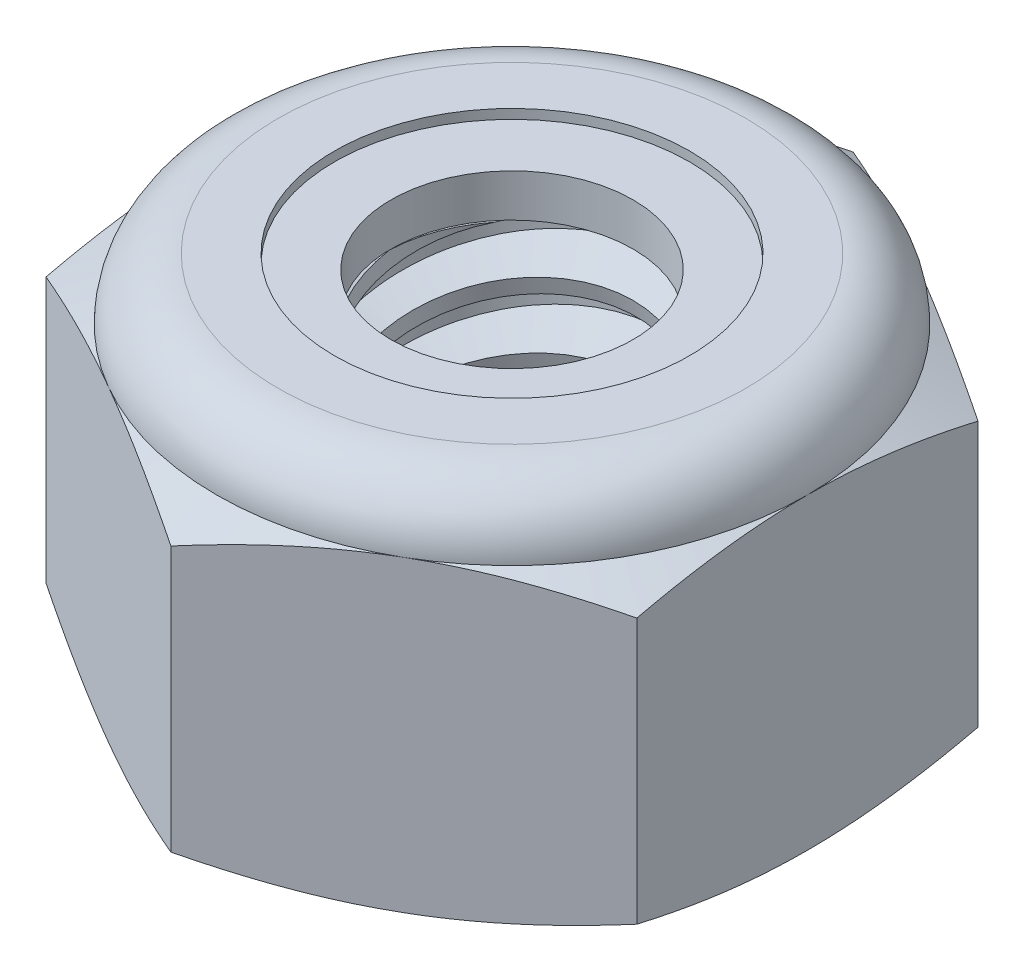
SolidWorks part; units mm, degrees
material "Alloy Steel"
ref_plane "Front" through (0, 0, 0) normal (0, 0, 1) x (1, 0, 0)
ref_plane "Top" through (0, 0, 0) normal (0, 1, 0) x (1, 0, 0)
ref_plane "Right" through (0, 0, 0) normal (1, 0, 0) x (0, 0, -1)
sketch "Sketch1" plane through (0, 0, 0) normal (0, 1, 0) x (1, 0, 0)
  line L1 (0, 5.4993) -> (-4.7625, 2.7496)
  line L2 (-4.7625, 2.7496) -> (-4.7625, -2.7496)
  line L3 (-4.7625, -2.7496) -> (0, -5.4993)
  line L4 (0, -5.4993) -> (4.7625, -2.7496)
  line L5 (4.7625, -2.7496) -> (4.7625, 2.7496)
  line L6 (4.7625, 2.7496) -> (0, 5.4993)
  circle A0 centre (0, 0) radius 4.7625 construction
  dimension "Hex Flats" = 9.525
extrude "Extrude1" add sketch "Sketch1" along normal blind 5.9531
sketch "Sketch2" plane through (0, 0, 0) normal (1, 0, 0) x (0, 0, -1)
  line L0 (-2.413, 0) -> (-2.413, 5.9531) construction
  line L1 (0, 0) -> (2.413, 0)
  line L2 (0, 0) -> (0, 5.9531)
  line L3 (0, 5.9531) -> (2.413, 5.9531)
  line L4 (2.413, 0) -> (2.413, 5.9531)
  line L5 (-2.7496, 5.9531) -> (2.7496, 5.9531) construction
  line L7 (0, -2.413) -> (0, 0) construction
  dimension "Thread Dia" = 4.826
revolve "Revolve1" add sketch "Sketch2" angle 360 about L7
sketch "Sketch3" plane through (0, 0, 0) normal (1, 0, 0) x (0, 0, -1)
  line L0 (2.413, 5.9531) -> (-2.413, 5.9531) construction
  line L1 (-2.413, 5.9531) -> (-2.413, 4.8948) construction
  line L2 (-2.413, 4.8948) -> (2.413, 5.9531) construction
  line L3 (2.413, 5.9531) -> (2.4413, 5.8239) construction
  line L4 (2.4413, 5.8239) -> (2.6397, 4.9194)
  line L5 (2.6397, 4.9194) -> (2.0093, 5.1197)
  line L6 (2.0093, 5.1197) -> (1.9526, 5.3781)
  line L7 (1.9526, 5.3781) -> (2.4413, 5.8239)
  line L8 (1.981, 5.2489) -> (2.5405, 5.3716) construction
  line L9 (2.413, 5.9531) -> (2.413, 5.3437) construction
  line L10 (2.413, 5.3437) -> (-2.413, 4.2853) construction
  line L11 (-2.413, 4.2853) -> (-2.413, 4.8948) construction
  line L12 (-0.2497, 5.9531) -> (0.2497, 3.6759) construction
  line L13 (-2.413, 0) -> (-2.413, 5.9531) construction
  line L14 (0, 5.9531) -> (2.413, 5.9531) construction
  line L15 (2.413, 0) -> (2.413, 5.9531) construction
  point P13 (0, 4.8145)
  dimension "D1" = 0.1323
  dimension "D2" = 0.2646
  dimension "Thread Pitch" = 1.0583
  dimension "D4" = 60
  dimension "D5" = 1.0583
revolve "Cut-Revolve1" cut sketch "Sketch3" angle 360 about L12
pattern_linear "LPattern1" count 6 spacing 1.0583 along (0, -1, 0) count 2 spacing 1.0583 along (0, 1, 0) of "Cut-Revolve1"
sketch "Sketch4" plane through (0, 0, 0) normal (1, 0, 0) x (0, 0, -1)
  line L0 (0, 5.9531) -> (2.413, 5.9531)
  line L1 (2.413, 5.9531) -> (1.9526, 5.7385)
  line L2 (1.9526, 5.7385) -> (1.9526, 0.2147)
  line L3 (1.9526, 0.2147) -> (2.413, 0)
  line L4 (2.413, 0) -> (0, 0)
  line L5 (0, 0) -> (0, 5.9531)
  line L6 (2.413, 0) -> (2.413, 5.9531) construction
  line L7 (0, 5.9531) -> (2.413, 5.9531) construction
  line L8 (0, 0) -> (2.413, 0) construction
  line L9 (0, 0) -> (0, 5.9531) construction
  line L10 (0, 5.9531) -> (0, 6.4611) construction
  dimension "D1" = 25
revolve "Cut-Revolve2" cut sketch "Sketch4" angle 360 about L10
combine bodies "Combine1" operation type subtract main body 112 bodies to subtract 111
sketch "Sketch5" plane through (0, 0, 0) normal (1, 0, 0) x (0, 0, -1)
  line L0 (0, 0) -> (4.7625, 0)
  line L1 (4.7625, 0) -> (5.4993, 0.3436)
  line L2 (5.4993, 0.3436) -> (5.4993, 4.6174)
  line L3 (5.4993, 4.6174) -> (4.7625, 4.9609)
  line L4 (3.7703, 5.9531) -> (3.7703, 7.2231)
  line L5 (3.7703, 7.2231) -> (6.7693, 7.2231)
  line L6 (6.7693, 7.2231) -> (6.7693, -1.27)
  line L7 (6.7693, -1.27) -> (0, -1.27)
  line L8 (0, -1.27) -> (0, 0)
  line L9 (4.7625, 4.9609) -> (4.7625, 0) construction
  line L10 (0, 0) -> (2.413, 0) construction
  line L13 (5.4993, 2.4805) -> (6.7693, 2.4805) construction
  line L14 (5.4993, 5.9531) -> (5.4993, 0) construction
  line L15 (0, 0) -> (0, 7.2231) construction
  line L20 (0, 7.2231) -> (3.7703, 7.2231) construction
  line L22 (0, 5.9531) -> (2.413, 5.9531) construction
  arc A0 (4.7625, 4.9609) -> (3.7703, 5.9531) centre (3.7703, 4.9609) ccw
  dimension "D1" = 25
  dimension "D2" = 1.27
  dimension "D3" = 5.9531
  dimension "D4" = 0.9922
revolve "Cut-Revolve3" cut sketch "Sketch5" angle 360 about L15
sketch "Sketch6" plane through (0, 0, 0) normal (1, 0, 0) x (0, 0, -1)
  line L0 (0, 4.9609) -> (4.6101, 4.9609)
  line L1 (3.7703, 5.8007) -> (2.8615, 5.8007)
  line L2 (0, 7.2231) -> (0, 4.9609)
  line L3 (2.8615, 7.2231) -> (0, 7.2231)
  line L4 (0, 7.2231) -> (3.7703, 7.2231) construction
  line L5 (0, 0) -> (0, 7.2231) construction
  line L6 (0, 7.2231) -> (0, 44.323) construction
  line L7 (2.8615, 5.8007) -> (2.8615, 7.2231)
  line L8 (3.7703, 5.9531) -> (3.7703, 5.8007) construction
  line L9 (2.8615, 5.8007) -> (1.9526, 5.8007) construction
  line L10 (1.9526, 5.8007) -> (1.9526, 5.7385) construction
  arc A0 (4.6101, 4.9609) -> (3.7703, 5.8007) centre (3.7703, 4.9609) ccw
  arc A1 (4.7625, 4.9609) -> (3.7703, 5.9531) centre (3.7703, 4.9609) ccw construction
  dimension "D1" = 0.1524
revolve "Cut-Revolve4" cut sketch "Sketch6" angle 360 about L6
sketch "Sketch7" plane through (0, 0, 0) normal (1, 0, 0) x (0, 0, -1)
  line L0 (1.9526, 5.0371) -> (4.5301, 5.0371)
  line L1 (3.7703, 5.7245) -> (1.9526, 5.7245)
  line L2 (1.9526, 5.7245) -> (1.9526, 5.0371)
  line L3 (1.9526, 5.0371) -> (0, 5.0371) construction
  line L4 (0, 5.0371) -> (0, 5.7245) construction
  line L5 (0, 5.7245) -> (1.9526, 5.7245) construction
  line L6 (1.9526, 5.0371) -> (1.9526, 4.9609) construction
  line L7 (0, 4.9609) -> (4.6101, 4.9609) construction
  line L8 (3.7703, 5.7245) -> (3.7703, 5.8007) construction
  arc A0 (4.5301, 5.0371) -> (3.7703, 5.7245) centre (3.7703, 4.9609) ccw
  arc A2 (4.6101, 4.9609) -> (3.7703, 5.8007) centre (3.7703, 4.9609) ccw construction
  dimension "D1" = 0.0762
revolve "Revolve2" add sketch "Sketch7" angle 360 about L4
equation "\"D1@Sketch3\"=\"Thread Pitch@Sketch3\"/8"
equation "\"D2@Sketch3\"=\"Thread Pitch@Sketch3\"/4"
equation "\"D5@Sketch3\"=\"Thread Pitch@Sketch3\""
equation "\"D4@LPattern1\"=\"Thread Pitch@Sketch3\""
equation "\"D3@LPattern1\"=\"Thread Pitch@Sketch3\""
equation "\"D1@LPattern1\"=\"Height@Extrude1\"/\"Thread Pitch@Sketch3\""
equation "\"D4@Sketch5\"=\"Height@Extrude1\"/6"
